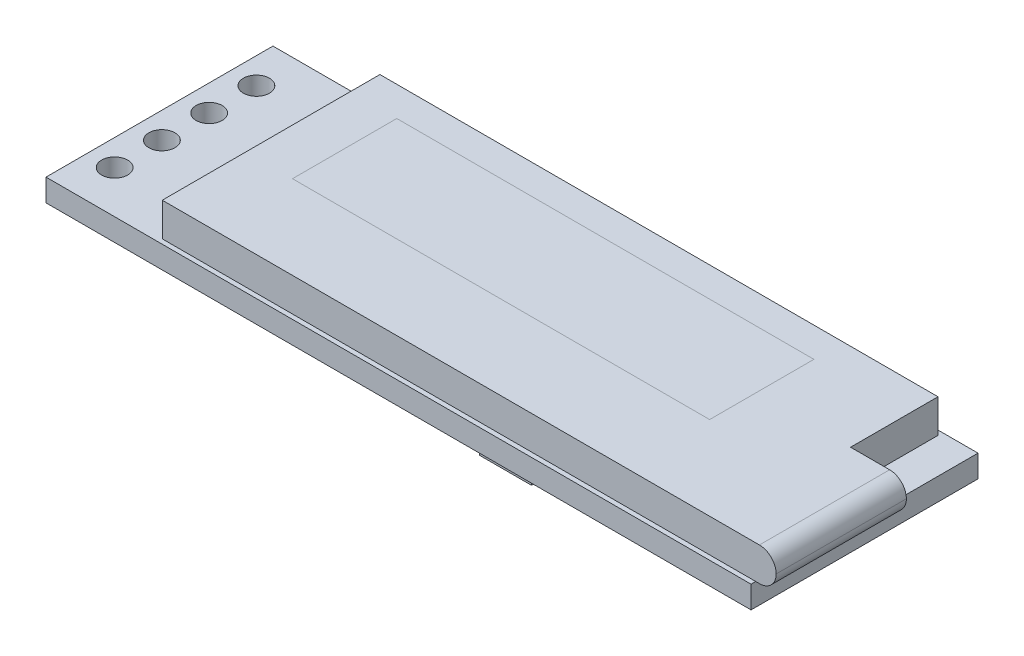
SolidWorks part; units mm, degrees
ref_plane "Спереди" through (0, 0, 0) normal (0, 0, 1) x (1, 0, 0)
ref_plane "Сверху" through (0, 0, 0) normal (0, 1, 0) x (1, 0, 0)
ref_plane "Справа" through (0, 0, 0) normal (1, 0, 0) x (0, 0, -1)
sketch "Эскиз1" plane through (0, 0, 0) normal (0, 1, 0) x (1, 0, 0)
  line L1 (-18.95, 6.1) -> (18.95, 6.1)
  line L2 (-18.95, 6.1) -> (-18.95, -6.1)
  line L3 (-18.95, -6.1) -> (18.95, -6.1)
  line L4 (18.95, 6.1) -> (18.95, -6.1)
  line L5 (-18.95, 6.1) -> (18.95, -6.1) construction
  line L6 (-18.95, -6.1) -> (18.95, 6.1) construction
  point P0 (0, 0)
  dimension "D1" = 37.9
  dimension "D2" = 12.2
extrude "Бобышка-Вытянуть1" add sketch "Эскиз1" along normal blind 1.2
sketch "Эскиз2" plane through (0, 1.2, 0) normal (0, 1, 0) x (1, 0, 0)
  line L1 (-12.95, 5.85) -> (17.05, 5.85)
  line L2 (-12.95, 5.85) -> (-12.95, -5.85)
  line L3 (-12.95, -5.85) -> (17.05, -5.85)
  line L4 (17.05, 5.85) -> (17.05, 1.15)
  line L5 (-12.95, 5.85) -> (17.05, -5.85) construction
  line L6 (-12.95, -5.85) -> (17.05, 5.85) construction
  line L8 (-18.95, 6.1) -> (-18.95, -6.1) construction
  line L10 (17.05, -5.85) -> (20.05, -5.85)
  line L12 (17.05, 1.15) -> (20.05, 1.15)
  line L13 (20.05, -5.85) -> (20.05, 1.15)
  point P0 (2.05, 0)
  dimension "D1" = 11.7
  dimension "D2" = 30
  dimension "D3" = 6
  dimension "D4" = 3
  dimension "D5" = 7
extrude "Бобышка-Вытянуть2" add sketch "Эскиз2" along normal blind 1.8
fillet "Скругление1" radius 0.9 2 edges at (20.05, 1.2, 2.35) (20.05, 3, 2.35)
sketch "Эскиз3" plane through (0, 3, 0) normal (0, 1, 0) x (1, 0, 0)
  line L0 (0.7619, 4.256) -> (11.9739, 4.256) construction
  line L1 (-10.45, 4.256) -> (11.9739, 4.256)
  line L2 (-10.45, 4.256) -> (-10.45, -1.35)
  line L3 (-10.45, -1.35) -> (11.9739, -1.35)
  line L4 (11.9739, 4.256) -> (11.9739, -1.35)
  line L5 (-10.45, 4.256) -> (11.9739, -1.35) construction
  line L6 (-10.45, -1.35) -> (11.9739, 4.256) construction
  line L7 (6.3679, 4.256) -> (11.9739, 4.256) construction
  line L8 (-12.95, 5.85) -> (-12.95, -5.85) construction
  line L9 (-12.95, -5.85) -> (18.95, -5.85) construction
  point P0 (0.7619, 1.453)
  dimension "D1" = 23.114
  dimension "D2" = 22.4239
  dimension "D3" = 5.606
  dimension "D4" = 2.5
  dimension "D5" = 4.5
split line "Разделяющая линия1"
sketch "Эскиз4" plane through (0, 1.2, 0) normal (0, 1, 0) x (1, 0, 0)
  line L0 (-18.95, 6.1) -> (-18.95, -6.1) construction
  line L1 (-17.55, 1.27) -> (-17.55, -1.27) construction
  circle A0 centre (-17.55, 3.81) radius 0.7
  circle A1 centre (-17.55, 1.27) radius 0.7
  circle A2 centre (-17.55, -1.27) radius 0.7
  circle A3 centre (-17.55, -3.81) radius 0.7
  point P10 (-17.55, 0)
  dimension "D2" = 1.4
  dimension "D3" = 2.54
  dimension "D4" = 1.4
  dimension "D1" = 4
extrude "Вырез-Вытянуть1" cut sketch "Эскиз4" against normal through all
sketch "Эскиз5" plane through (0, 0, 0) normal (0, -1, 0) x (1, 0, 0)
  line L0 (18.95, -6.1) -> (-18.95, -6.1) construction
  line L1 (3.65, 5.4) -> (6.45, 5.4)
  line L2 (3.65, 5.4) -> (3.65, -4.7)
  line L3 (3.65, -4.7) -> (6.45, -4.7)
  line L4 (6.45, 5.4) -> (6.45, -4.7)
  line L5 (3.65, 5.4) -> (6.45, -4.7) construction
  line L6 (3.65, -4.7) -> (6.45, 5.4) construction
  line L7 (-3.45, 4.7) -> (-0.65, 4.7)
  line L8 (-3.45, 4.7) -> (-3.45, -3.3)
  line L9 (-3.45, -3.3) -> (-0.65, -3.3)
  line L10 (-0.65, 4.7) -> (-0.65, -3.3)
  line L11 (-3.45, 4.7) -> (-0.65, -3.3) construction
  line L12 (-3.45, -3.3) -> (-0.65, 4.7) construction
  line L13 (-11.55, 4.3) -> (-7.55, 4.3)
  line L14 (-11.55, 4.3) -> (-11.55, -3.1)
  line L15 (-11.55, -3.1) -> (-7.55, -3.1)
  line L16 (-7.55, 4.3) -> (-7.55, -3.1)
  line L17 (-11.55, 4.3) -> (-7.55, -3.1) construction
  line L18 (-11.55, -3.1) -> (-7.55, 4.3) construction
  line L19 (18.95, 6.1) -> (18.95, -6.1) construction
  line L20 (-18.95, 6.1) -> (18.95, 6.1) construction
  line L21 (-18.95, -6.1) -> (-18.95, 6.1) construction
  point P0 (5.05, 0.35)
  point P5 (-2.05, 0.7)
  point P10 (-9.55, 0.6)
  dimension "D1" = 10.1
  dimension "D2" = 1.4
  dimension "D3" = 12.5
  dimension "D4" = 2.8
  dimension "D5" = 4
  dimension "D6" = 2.8
  dimension "D7" = 1.4
  dimension "D8" = 8
  dimension "D9" = 15.5
  dimension "D10" = 7.4
  dimension "D11" = 1.8
  dimension "D12" = 7.4
extrude "Бобышка-Вытянуть3" add sketch "Эскиз5" along normal blind 0.8
